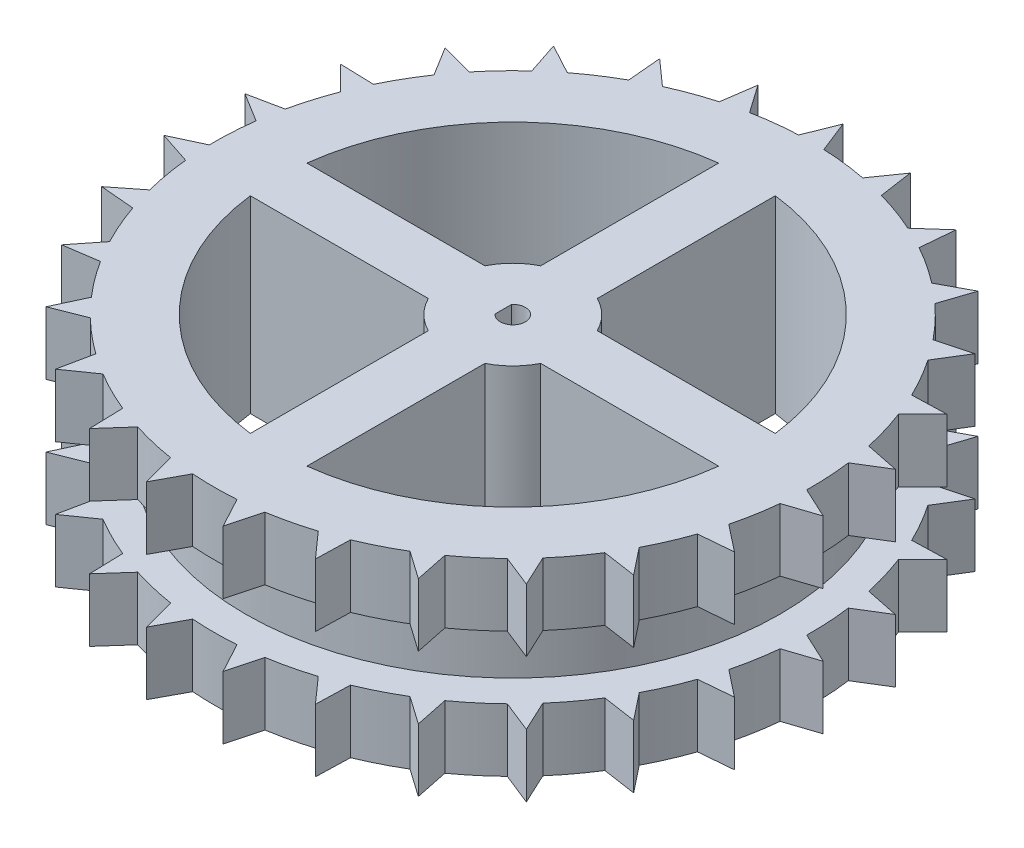
SolidWorks part; units mm, degrees
ref_plane "Front Plane" through (0, 0, 0) normal (0, 0, 1) x (1, 0, 0)
ref_plane "Top Plane" through (0, 0, 0) normal (0, 1, 0) x (1, 0, 0)
ref_plane "Right Plane" through (0, 0, 0) normal (1, 0, 0) x (0, 0, -1)
sketch "Sketch1" plane through (0, 0, 0) normal (0, 1, 0) x (1, 0, 0)
  line L0 (2, 47.4579) -> (0, 52.5)
  line L1 (0, 52.5) -> (-2, 47.4579)
  line L2 (0, 52.5) -> (0, 47.5) construction
  line L3 (-2, 47.4579) -> (0, 47.5) construction
  line L4 (0, 47.5) -> (2, 47.4579) construction
  line L5 (-2, 47.4579) -> (0, 47.5) construction
  line L6 (0, 47.5) -> (2, 47.4579) construction
  line L7 (12.8906, 45.7174) -> (12.1073, 51.0849)
  line L8 (12.1073, 51.0849) -> (8.9984, 46.6399)
  line L9 (23.0863, 41.5123) -> (23.562, 46.9157)
  line L10 (23.562, 46.9157) -> (19.5118, 43.3075)
  line L11 (32.0374, 35.0693) -> (33.7463, 40.2173)
  line L12 (33.7463, 40.2173) -> (28.9732, 37.6404)
  line L13 (39.2614, 26.7356) -> (42.1115, 31.3508)
  line L14 (42.1115, 31.3508) -> (36.8727, 29.9441)
  line L15 (44.3687, 16.9607) -> (48.2063, 20.7942)
  line L16 (48.2063, 20.7942) -> (42.7844, 20.6335)
  line L17 (47.0842, 6.2714) -> (51.7024, 9.1165)
  line L18 (51.7024, 9.1165) -> (46.3896, 10.2106)
  line L19 (47.2613, -4.756) -> (52.4112, -3.0526)
  line L20 (52.4112, -3.0526) -> (47.4939, -0.7628)
  line L21 (44.8905, -15.5271) -> (50.2944, -15.0572)
  line L22 (50.2944, -15.0572) -> (46.0378, -11.6951)
  line L23 (40.0997, -25.461) -> (45.4663, -26.25)
  line L24 (45.4663, -26.25) -> (42.0997, -21.9969)
  line L25 (33.1471, -34.0223) -> (38.1871, -36.0277)
  line L26 (38.1871, -36.0277) -> (35.8921, -31.1128)
  line L27 (24.4076, -40.7495) -> (28.8492, -43.8631)
  line L28 (28.8492, -43.8631) -> (27.7495, -38.5515)
  line L29 (14.3522, -45.2799) -> (17.9561, -49.3339)
  line L30 (17.9561, -49.3339) -> (18.1109, -43.9118)
  line L31 (3.523, -47.3692) -> (6.0949, -52.145)
  line L32 (6.0949, -52.145) -> (7.496, -46.9048)
  line L33 (-7.496, -46.9048) -> (-6.0949, -52.145)
  line L34 (-6.0949, -52.145) -> (-3.523, -47.3692)
  line L35 (-18.1109, -43.9118) -> (-17.9561, -49.3339)
  line L36 (-17.9561, -49.3339) -> (-14.3522, -45.2799)
  line L37 (-27.7495, -38.5515) -> (-28.8492, -43.8631)
  line L38 (-28.8492, -43.8631) -> (-24.4076, -40.7495)
  line L39 (-35.8921, -31.1128) -> (-38.1871, -36.0277)
  line L40 (-38.1871, -36.0277) -> (-33.1471, -34.0223)
  line L41 (-42.0997, -21.9969) -> (-45.4663, -26.25)
  line L42 (-45.4663, -26.25) -> (-40.0997, -25.461)
  line L43 (-46.0378, -11.6951) -> (-50.2944, -15.0572)
  line L44 (-50.2944, -15.0572) -> (-44.8905, -15.5271)
  line L45 (-47.4939, -0.7628) -> (-52.4112, -3.0526)
  line L46 (-52.4112, -3.0526) -> (-47.2613, -4.756)
  line L47 (-46.3896, 10.2106) -> (-51.7024, 9.1165)
  line L48 (-51.7024, 9.1165) -> (-47.0842, 6.2714)
  line L49 (-42.7844, 20.6335) -> (-48.2063, 20.7942)
  line L50 (-48.2063, 20.7942) -> (-44.3687, 16.9607)
  line L51 (-36.8727, 29.9441) -> (-42.1115, 31.3508)
  line L52 (-42.1115, 31.3508) -> (-39.2614, 26.7356)
  line L53 (-28.9732, 37.6404) -> (-33.7463, 40.2173)
  line L54 (-33.7463, 40.2173) -> (-32.0374, 35.0693)
  line L55 (-19.5118, 43.3075) -> (-23.562, 46.9157)
  line L56 (-23.562, 46.9157) -> (-23.0863, 41.5123)
  line L57 (-8.9984, 46.6399) -> (-12.1073, 51.0849)
  line L58 (-12.1073, 51.0849) -> (-12.8906, 45.7174)
  line L59 (0, 10) -> (0, 37.5) construction
  line L60 (-4.5, 37.229) -> (-4.5, 8.9303)
  line L61 (4.5, 37.229) -> (4.5, 8.9303)
  line L62 (37.229, -4.5) -> (8.9303, -4.5)
  line L63 (37.229, 4.5) -> (8.9303, 4.5)
  line L64 (-4.5, -37.229) -> (-4.5, -8.9303)
  line L65 (4.5, -37.229) -> (4.5, -8.9303)
  line L66 (-37.229, 4.5) -> (-8.9303, 4.5)
  line L67 (-37.229, -4.5) -> (-8.9303, -4.5)
  line L68 (-1.3648, 1.2583) -> (-1.5, 1.3229)
  line L69 (-1.5, 1.3229) -> (-1.5, -1.3229)
  circle A0 centre (0, 0) radius 47.5
  circle A1 centre (0, 0) radius 37.5
  circle A2 centre (0, 0) radius 5
  circle A3 centre (0, 0) radius 2
  circle A4 centre (0, 0) radius 10
  circle A5 centre (0, 0) radius 42.5
  point P88 (0, 0)
  point P111 (0, 0)
  dimension "D1" = 95
  dimension "D5" = 75
  dimension "D6" = 10
  dimension "D7" = 4
  dimension "D8" = 20
  dimension "D9" = 4
  dimension "D11" = 0.5
  dimension "D12" = 5
  dimension "D2" = 5
  dimension "D3" = 2
  dimension "D10" = 9
  dimension "D4" = 27
extrude "Boss-Extrude2" add sketch "Sketch1" along normal blind 10 contours A2 A3 | L69 A3 | A4 A2 | A4 L62 A1 L63 | A4 L64 A1 L65 | A4 L66 A1 L67 | A4 L61 A1 L60 | A5 A1 | A0 region at (5.3584, 0, -45.8444) region at (0, 0, -23.5289) region at (0, 0, -9.7172) region at (-23.5289, 0, 0) region at (23.5289, 0, 0) region at (0, 0, 23.5289) region at (-1.7023, 0, 0) region at (-4.8586, 0, 0) region at (-41.2979, 0, 0)
extrude "Boss-Extrude3" add sketch "Sketch1<7>" along normal blind 20 contours A4 A2 | A4 L62 A1 L63 | A4 L64 A1 L65 | A4 L66 A1 L67 | A4 L61 A1 L60 | A2 A3 | L69 A3 | A5 A1 region at (0, 0, -23.5289) region at (0, 0, -9.7172) region at (-23.5289, 0, 0) region at (23.5289, 0, 0) region at (0, 0, 23.5289) region at (-1.7023, 0, 0) region at (-4.8586, 0, 0) region at (-41.2979, 0, 0)
sketch "Sketch1<7>" plane through (0, 0, 0) normal (0, 1, 0) x (1, 0, 0) same geometry as "Sketch1"
extrude "Boss-Extrude4" add sketch "Sketch1<8>" along normal blind 10 from surface contours A4 A2 | A2 A3 | L69 A3 | A4 L62 A1 L63 | A4 L64 A1 L65 | A4 L66 A1 L67 | A4 L61 A1 L60 | A5 A1 | A0 region at (5.3584, 0, -45.8444) region at (0, 0, -23.5289) region at (0, 0, -9.7172) region at (-23.5289, 0, 0) region at (23.5289, 0, 0) region at (0, 0, 23.5289) region at (-1.7023, 0, 0) region at (-4.8586, 0, 0) region at (-41.2979, 0, 0) starting at face at (-15.2918, 20, 15.2918)
sketch "Sketch1<8>" plane through (0, 0, 0) normal (0, 1, 0) x (1, 0, 0) same geometry as "Sketch1"
extrude "Boss-Extrude6" add sketch "Sketch1<10>" along normal blind 10 contours A0 L57 L58 region at (-11.3365, 0, -47.8323)
sketch "Sketch1<10>" plane through (0, 0, 0) normal (0, 1, 0) x (1, 0, 0) same geometry as "Sketch1"
pattern_circular "CirPattern1" count 27 over 360 about axis through (0, 30, 0) along (0, 1, 0) of "Boss-Extrude6"
extrude "Boss-Extrude7" add sketch "Sketch1<12>" along normal blind 10 from surface contours A0 L57 L58 region at (-11.3365, 0, -47.8323) starting at face at (0, 20, 42.5)
sketch "Sketch1<12>" plane through (0, 0, 0) normal (0, 1, 0) x (1, 0, 0) same geometry as "Sketch1"
pattern_circular "CirPattern2" count 27 over 360 about axis through (0, 30, 0) along (0, 1, 0) of "Boss-Extrude7"
